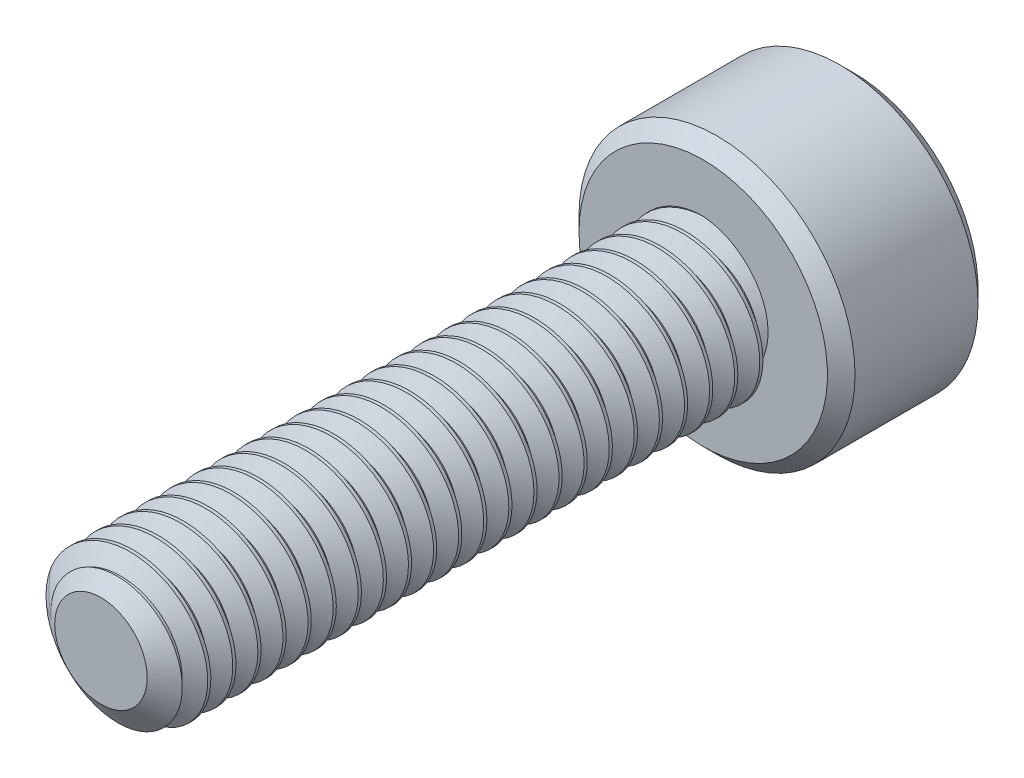
SolidWorks part; units mm, degrees
note: '?' marks a value the reader was unsure of.
other "DetailItem1"
material "Bolt metal"
ref_plane "Front Plane" through (0, 0, 0) normal (0, 0, 1) x (1, 0, 0)
ref_plane "Top Plane" through (0, 0, 0) normal (0, 1, 0) x (1, 0, 0)
ref_plane "Right Plane" through (0, 0, 0) normal (1, 0, 0) x (0, 0, -1)
sketch "Sketch1" plane through (0, 0, 0) normal (0, 0, 1) x (1, 0, 0)
  circle A0 centre (0, 0) radius 1.5
  dimension "OD" = 3
extrude "Extrude1" add sketch "Sketch1" against normal blind 12
sketch "Sketch2" plane through (0, 0, 0) normal (0, 0, 1) x (1, 0, 0)
  circle A0 centre (0, 0) radius 1.5 construction
  circle A1 centre (0, 0) radius 1.5
curve "Helix/Spiral1" pitch 0.5 height 12.5 radius 1.5 centre (0, 0, 0) axis (0, 0, -1) start towards (0, 1, 0) parameters "pitch"=0.5
sketch "Sketch3" plane through (0, 0, 0) normal (1, 0, 0) x (0, 0, -1)
  line L0 (-0.4375, 1.5) -> (-0.25, 1.1752)
  line L1 (-0.25, 1.1752) -> (-0.1875, 1.1752)
  line L2 (-0.1875, 1.1752) -> (0, 1.5)
  line L3 (-0.4375, 1.5) -> (0, 1.5)
  line L4 (-0.2188, 1.5) -> (-0.2188, 1.1752) construction
  line L5 (-0.3438, 1.3376) -> (-0.0938, 1.3376) construction
  line L6 (0, 1.5) -> (0, -1.5) construction
  dimension "D1" = 0.0625
  dimension "D2" = 0.25
  dimension "D3" = 60
sweep "Cut-Sweep1" cut profiles "Sketch3" path "Helix/Spiral1" align with end faces yes
sketch "Sketch4" plane through (0, 0, 0) normal (1, 0, 0) x (0, 0, -1)
  line L0 (0.4053, 1.5) -> (0, 0.9212)
  line L1 (0, 0.9212) -> (0, 1.5)
  line L2 (0.4053, 1.5) -> (0, 1.5)
  line L3 (-0.4375, 1.5) -> (0, 1.5) construction
  line L4 (0, 0) -> (7.0209, 0) construction
  dimension "D1" = 55
  dimension "D2" = 0.254
revolve "Cut-Revolve1" cut sketch "Sketch4" angle 360 about L4
sketch "Sketch6" plane through (0, 0, -12) normal (0, 0, -1) x (-1, 0, 0)
  circle A0 centre (0, 0) radius 2.75
  dimension "head dia" = 5.5
extrude "Extrude2" add sketch "Sketch6" along normal blind 3
sketch "Sketch7" plane through (0, 0, -15) normal (0, 0, -1) x (-1, 0, 0)
  line L1 (0, 1.4434) -> (-1.25, 0.7217)
  line L2 (-1.25, 0.7217) -> (-1.25, -0.7217)
  line L3 (-1.25, -0.7217) -> (0, -1.4434)
  line L4 (0, -1.4434) -> (1.25, -0.7217)
  line L5 (1.25, -0.7217) -> (1.25, 0.7217)
  line L6 (1.25, 0.7217) -> (0, 1.4434)
  circle A0 centre (0, 0) radius 1.25 construction
  dimension "hex dia" = 2.5
extrude "Cut-Extrude1" cut sketch "Sketch7" against normal blind 1.875
sketch "Sketch8" plane through (0, 0, -15) normal (0, 0, -1) x (-1, 0, 0)
  circle A0 centre (0, 0) radius 1.4434
extrude "Cut-Extrude2" cut sketch "Sketch8" against normal through all draft 45
chamfer "Chamfer1" distance 0.275 angle 45 2 edges at (-2.75, 0, -15) (-2.75, 0, -12)
sketch "Sketch10" plane through (0, 0, -12) normal (0, 0, 1) x (1, 0, 0)
  circle A1 centre (0, 0) radius 1.5
  circle A2 centre (0, 0) radius 1.5
  dimension "D1" = 0
ref_plane "Plane1" through (0, 0, -22) normal (0, 0, 1) x (1, 0, 0)
extrude "partial thread" [suppressed] add sketch "Sketch10" along normal up to surface (58 mm away) separate body
chamfer "Chamfer2" [suppressed] distance 0.06 angle 45
combine bodies "Combine1" [suppressed] operation type? add bodies to combine 107 108
sketch "Sketch9" plane through (0, 0, 0) normal (1, 0, 0) x (0, 0, -1)
  line L0 (0, 1.5) -> (0, -1.5) construction
  line L1 (1.25, 1.5) -> (1.25, -1.5) construction
  dimension "D1" = 1.25
equation "\"D3@Helix/Spiral1\" = \"screw length@Extrude1\"+\"pitch@Helix/Spiral1\""
equation "\"D1@Sketch3\" = \"pitch@Helix/Spiral1\"*.125"
equation "\"D2@Sketch3\" = \"pitch@Helix/Spiral1\"*.5"
equation "\"D1@Cut-Extrude1\" = \"hex dia@Sketch7\"*.75"
equation "\"D1@Chamfer1\" = \"head dia@Sketch6\"*.05"
equation "\"D1@Sketch9\" = \"pitch@Helix/Spiral1\"*2.5"
equation "\"D1@Chamfer2\"=\"OD@Sketch1\"*.02"
